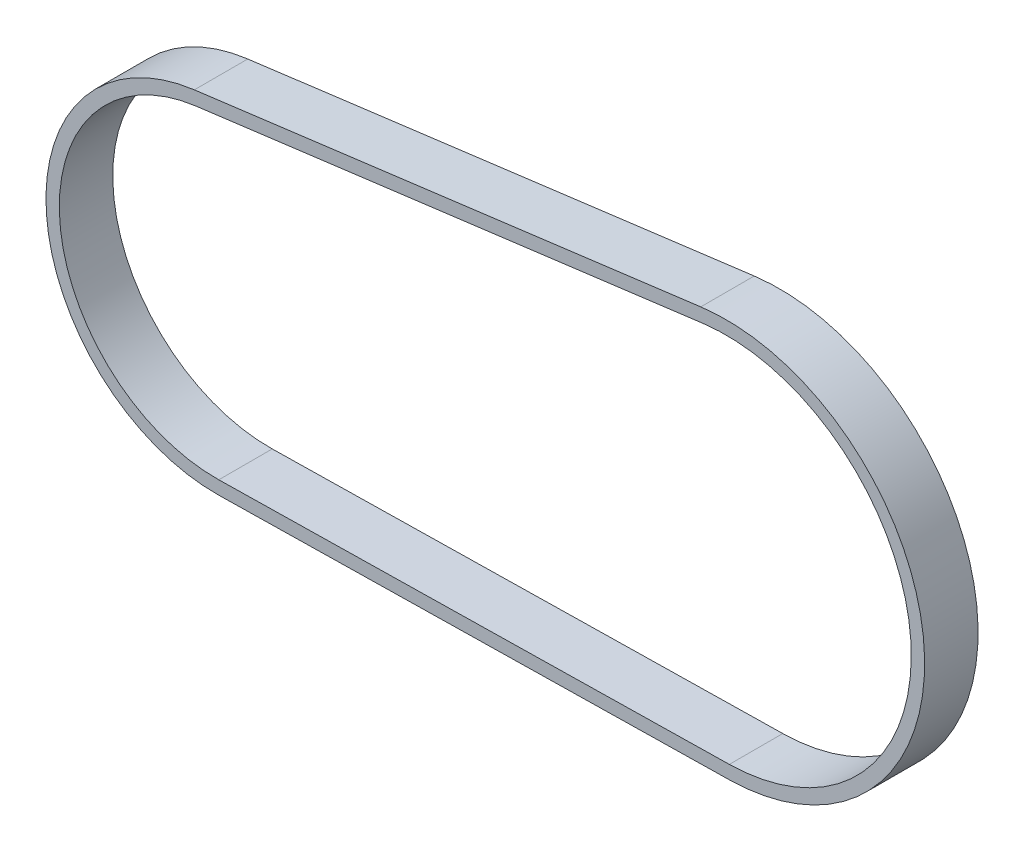
SolidWorks part; units mm, degrees
ref_plane "Front Plane" through (0, 0, 0) normal (0, 0, 1) x (1, 0, 0)
ref_plane "Top Plane" through (0, 0, 0) normal (0, 1, 0) x (1, 0, 0)
ref_plane "Right Plane" through (0, 0, 0) normal (1, 0, 0) x (0, 0, -1)
sketch "Sketch2" plane through (0, 0, 0) normal (0, 0, 1) x (1, 0, 0)
  line L0 (0, 0) -> (1, 0) construction
  line L1 (0, 0) -> (0, 1) construction
  line L6 (-59.7014, 14.7715) -> (-2.8482, 22.0989)
  line L7 (0.384, -22.2784) -> (-56.931, -23.2662)
  arc A2 (-2.8482, 22.0989) -> (0.384, -22.2784) centre (0, 0) cw
  arc A4 (-56.931, -23.2662) -> (-59.7014, 14.7715) centre (-57.2601, -4.1704) cw
extrude "Extrude-Thin1" add sketch "Sketch2" against normal blind 6 thin thin type one direction reverse wall 1.5
